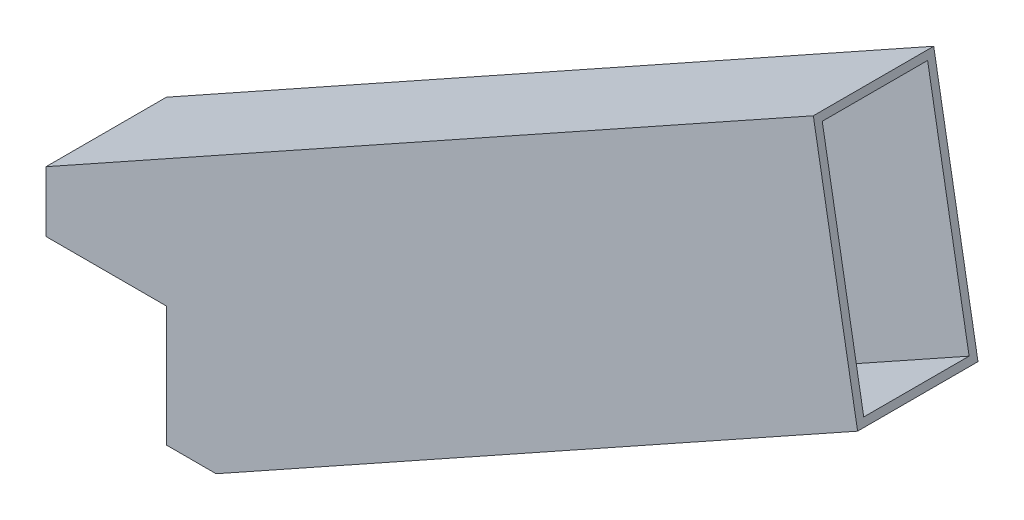
SolidWorks part; units mm, degrees
material "6061-T6 (SS)"
ref_plane "Front" through (0, 0, 0) normal (0, 0, 1) x (1, 0, 0)
ref_plane "Top" through (0, 0, 0) normal (0, 1, 0) x (1, 0, 0)
ref_plane "Right" through (0, 0, 0) normal (1, 0, 0) x (0, 0, -1)
sketch "Sketch1" plane through (0, 0, 0) normal (0, 0, 1) x (1, 0, 0)
  line L0 (180.1964, -98.3828) -> (139.6492, 131.572) construction
  line L1 (0, 0) -> (-50.8, 0) construction
  line L2 (0, 0) -> (0, 25.4) construction
  line L3 (0, 25.4) -> (-50.8, 25.4) construction
  line L4 (-50.8, 0) -> (-50.8, 25.4) construction
  line L5 (180.1964, -98.3828) -> (205.5964, -98.3828) construction
  line L6 (139.6492, 131.572) -> (-22.225, 41.33)
  line L7 (148.9866, 78.6168) -> (13.6607, 3.175)
  line L9 (139.6492, 131.572) -> (148.9866, 78.6168)
  line L11 (3.175, 3.175) -> (3.175, 28.575)
  line L12 (3.175, 28.575) -> (-22.225, 28.575) construction
  line L15 (-22.225, 28.575) -> (3.175, 28.575)
  line L16 (-50.8, 25.4) -> (-45.1047, 28.575) construction
  line L17 (-22.225, 41.33) -> (-22.225, 28.575)
  line L18 (3.175, 3.175) -> (13.6607, 3.175)
  point P11 (0, 0)
  point P13 (0, 0)
  dimension "D1" = 50.8
  dimension "D2" = 25.4
  dimension "D3" = 100
  dimension "D4" = 106.172
  dimension "D5" = 139.6492
  dimension "D6" = 25.4
  dimension "D7" = 233.5022
  dimension "D8" = 50.8
  dimension "D9" = 70.861
  dimension "D10" = 218.0445
  dimension "D11" = 3.175
  dimension "D12" = 3.175
  dimension "D13" = 25.4
  dimension "D14" = 25.4
extrude "Boss-Extrude1" add sketch "Sketch1" along normal blind 25.4
shell "Shell1" thickness 1.5875 removed face at (-9.525, 28.575, 12.7) removed face at (3.175, 15.875, 12.7) removed face at (144.3179, 105.0944, 12.7) removed face at (8.4179, 3.175, 12.7) removed face at (-22.225, 34.9525, 12.7)
